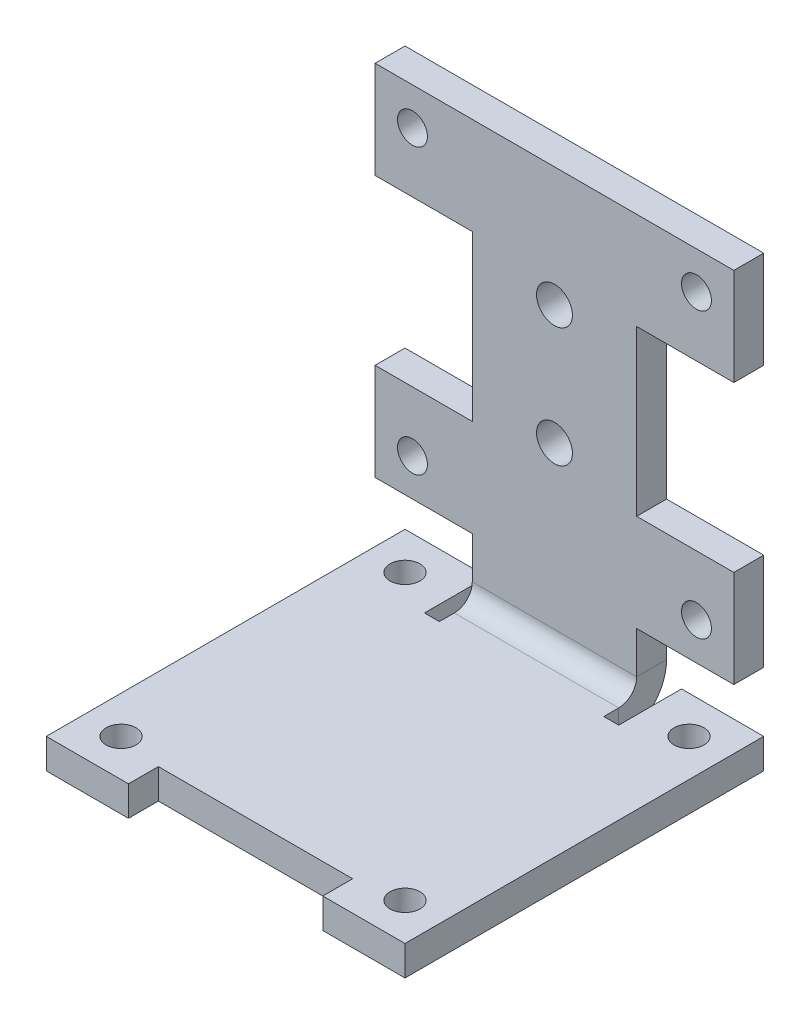
SolidWorks part; units mm, degrees
note: The reader was unsure of these and kept them because the rebuilt part matched: flange length of "边线-法兰1".
ref_plane "前视基准面" through (0, 0, 0) normal (0, 0, 1) x (1, 0, 0)
ref_plane "上视基准面" through (0, 0, 0) normal (0, 1, 0) x (1, 0, 0)
ref_plane "右视基准面" through (0, 0, 0) normal (1, 0, 0) x (0, 0, -1)
other "Configuration Table"
sketch "草图1" plane through (0, 0, 0) normal (0, 1, 0) x (1, 0, 0)
  line L0 (-16.25, 25) -> (-16.25, 30)
  line L1 (-30, -30) -> (-16.25, -30)
  line L2 (-30, -30) -> (-30, 30)
  line L3 (-30, 30) -> (-16.25, 30)
  line L4 (30, -30) -> (30, 30)
  line L5 (-30, -30) -> (30, 30) construction
  line L6 (-30, 30) -> (30, -30) construction
  line L7 (-23.75, -23.75) -> (23.75, -23.75) construction
  line L8 (-23.75, -23.75) -> (-23.75, 23.75) construction
  line L9 (-23.75, 23.75) -> (23.75, 23.75) construction
  line L10 (23.75, -23.75) -> (23.75, 23.75) construction
  line L11 (-23.75, -23.75) -> (23.75, 23.75) construction
  line L12 (-23.75, 23.75) -> (23.75, -23.75) construction
  line L14 (-16.25, -30) -> (-16.25, -25)
  line L16 (16.25, -30) -> (16.25, -25)
  line L17 (-16.25, -30) -> (16.25, 30) construction
  line L18 (-16.25, 30) -> (16.25, -30) construction
  line L19 (-16.25, -25) -> (16.25, -25)
  line L21 (-16.25, 25) -> (16.25, 25)
  line L23 (-16.25, -25) -> (16.25, 25) construction
  line L24 (-16.25, 25) -> (16.25, -25) construction
  line L26 (16.25, 25) -> (16.25, 30)
  line L27 (16.25, -30) -> (30, -30)
  line L28 (16.25, 30) -> (30, 30)
  circle A0 centre (-23.75, 23.75) radius 2.5
  circle A1 centre (23.75, 23.75) radius 2.5
  circle A2 centre (-23.75, -23.75) radius 2.5
  circle A3 centre (23.75, -23.75) radius 2.5
  point P0 (0, 0)
  point P6 (0, 0)
  point P15 (0, 0)
  point P20 (0, 0)
  dimension "D4" = 5
  dimension "D5" = 5
  dimension "D6" = 5
  dimension "D7" = 5
  dimension "D1" = 60
  dimension "D2" = 60
  dimension "D3" = 47.5
  dimension "D8" = 32.5
  dimension "D9" = 50
base flange "基体-法兰1" sketch "草图1" thickness 5 reverse thickness direction no parameters "D1"=0.7366
edge flange "边线-法兰1" sketch "草图8" flange angle 90 flange length 75 flange position material outside bend radius 3 thickness 5 parameters "D6"=10
sketch "草图8" plane through (0, 0, -25) normal (0, 0, -1) x (-1, 0, 0)
  line L5 (-16.25, 0) -> (16.25, 0) construction
  line L6 (-13.75, 70) -> (13.75, 70)
  line L7 (-13.75, 70) -> (-13.75, 0)
  line L8 (-13.75, 0) -> (13.75, 0)
  line L9 (13.75, 70) -> (13.75, 0)
  point P6 (0, 70)
  dimension "D1" = 27.5
  dimension "D2" = 70
bend "边线折弯1" bend radius 3 bend angle 90 parameters "D5"=1
sketch "草图9" plane through (0, 0, 0) normal (0, 0, 1) x (1, 0, 0)
  line L0 (-13.75, 70) -> (13.75, 70) construction
  line L1 (30, 70) -> (-30, 70) construction
  line L2 (30, 70) -> (30, 10) construction
  line L3 (30, 10) -> (-30, 10) construction
  line L4 (-30, 70) -> (-30, 10) construction
  line L5 (-13.75, 3) -> (-13.75, 70) construction
  line L6 (-30, 70) -> (-13.75, 70)
  line L7 (-30, 70) -> (-30, 53.75)
  line L8 (-30, 53.75) -> (-13.75, 53.75)
  line L9 (-13.75, 70) -> (-13.75, 53.75)
  line L10 (13.75, 70) -> (13.75, 3) construction
  line L11 (30, 70) -> (13.75, 70)
  line L12 (30, 70) -> (30, 53.75)
  line L13 (30, 53.75) -> (13.75, 53.75)
  line L14 (13.75, 70) -> (13.75, 53.75)
  line L16 (-30, 10) -> (-13.75, 10)
  line L17 (-30, 10) -> (-30, 26.25)
  line L18 (-30, 26.25) -> (-13.75, 26.25)
  line L19 (-13.75, 10) -> (-13.75, 26.25)
  line L20 (30, 10) -> (13.75, 10)
  line L21 (30, 10) -> (30, 26.25)
  line L22 (30, 26.25) -> (13.75, 26.25)
  line L23 (13.75, 10) -> (13.75, 26.25)
  point P6 (0, 70)
  dimension "D1" = 60
  dimension "D2" = 60
  dimension "D3" = 16.25
  dimension "D4" = 16.25
extrude "凸台-拉伸1" add sketch "草图9" along normal up to surface (5 mm away) from surface at -30 up to face at (0, 36.5, -25) starting at face at (0, 36.5, -30)
sketch "草图10" plane through (0, 0, 0) normal (0, 0, 1) x (1, 0, 0)
  line L5 (-30, 70) -> (30, 10) construction
  line L6 (30, 70) -> (-30, 10) construction
  line L7 (0, 30) -> (0, 50) construction
  circle A0 centre (0, 50) radius 3
  circle A1 centre (0, 30) radius 3
  point P13 (0, 40)
  dimension "D2" = 6
  dimension "D3" = 6
  dimension "D1" = 20
extrude "切除-拉伸1" cut sketch "草图10" against normal up to surface (5 mm away) from surface
sketch "草图11" plane through (0, 0, 0) normal (0, 0, 1) x (1, 0, 0)
  line L0 (30, 10) -> (-30, 70) construction
  line L1 (-30, 10) -> (30, 70) construction
  line L3 (-23.75, 16.25) -> (23.75, 16.25) construction
  line L4 (-23.75, 16.25) -> (-23.75, 63.75) construction
  line L5 (-23.75, 63.75) -> (23.75, 63.75) construction
  line L6 (23.75, 16.25) -> (23.75, 63.75) construction
  line L7 (-23.75, 16.25) -> (23.75, 63.75) construction
  line L8 (-23.75, 63.75) -> (23.75, 16.25) construction
  circle A0 centre (-23.75, 16.25) radius 2.5
  circle A1 centre (-23.75, 63.75) radius 2.5
  circle A2 centre (23.75, 63.75) radius 2.5
  circle A3 centre (23.75, 16.25) radius 2.5
  point P8 (0, 40)
  dimension "D2" = 5
  dimension "D3" = 5
  dimension "D4" = 5
  dimension "D5" = 5
  dimension "D1" = 47.5
extrude "切除-拉伸2" cut sketch "草图11" against normal up to surface (5 mm away) from surface
sketch "折弯-线1" plane through (0, 0, 0) normal (0, 1, 0) x (1, 0, 0)
sketch "边界框1" plane through (0, 0, 0) normal (0, 1, 0) x (1, 0, 0)
sheet metal parameters "钣金6" thickness 5 parameters "D1"=0.7366
flat pattern "平板型式6" [suppressed]
sketch "折弯-线2" plane through (0, 0, 0) normal (0, 1, 0) x (1, 0, 0)
sketch "边界框2" [suppressed] plane through (0, 0, 0) normal (0, 1, 0) x (1, 0, 0)
sheet metal parameters "钣金7" thickness 5 parameters "D1"=0.7366
flat pattern "平板型式6" [suppressed]
sketch "折弯-线2" plane through (0, 0, 0) normal (0, 1, 0) x (1, 0, 0)
sketch "边界框2" [suppressed] plane through (0, 0, 0) normal (0, 1, 0) x (1, 0, 0)
bend of the flat pattern "展平-<边线折弯1>1"
sheet metal parameters "钣金8" thickness 5 parameters "D1"=0.7366
flat pattern "平板型式6" [suppressed]
sketch "折弯-线2" plane through (0, 0, 0) normal (0, 1, 0) x (1, 0, 0)
sketch "边界框2" [suppressed] plane through (0, 0, 0) normal (0, 1, 0) x (1, 0, 0)
bend of the flat pattern "展平-<边线折弯1>1"
sheet metal parameters "钣金9" thickness 5 parameters "D1"=0.7366
flat pattern "平板型式6" [suppressed]
sketch "折弯-线2" plane through (0, 0, 0) normal (0, 1, 0) x (1, 0, 0)
sketch "边界框2" [suppressed] plane through (0, 0, 0) normal (0, 1, 0) x (1, 0, 0)
bend of the flat pattern "展平-<边线折弯1>1"
sheet metal parameters "钣金10" thickness 5 parameters "D1"=0.7366
flat pattern "平板型式6" [suppressed]
sketch "折弯-线2" plane through (0, 0, 0) normal (0, 1, 0) x (1, 0, 0)
sketch "边界框2" [suppressed] plane through (0, 0, 0) normal (0, 1, 0) x (1, 0, 0)
bend of the flat pattern "展平-<边线折弯1>1"
